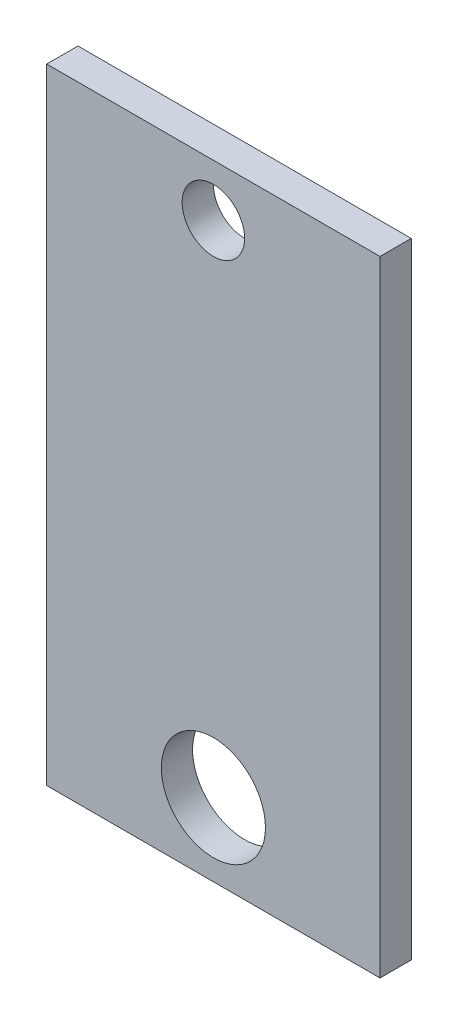
SolidWorks part; units mm, degrees
ref_plane "Спереди (XY) " through (0, 0, 0) normal (0, 0, 1) x (1, 0, 0)
ref_plane "Сверху (XZ)" through (0, 0, 0) normal (0, 1, 0) x (1, 0, 0)
ref_plane "Справа (ZY)" through (0, 0, 0) normal (1, 0, 0) x (0, 0, -1)
sketch "Эскиз1" plane through (0, 0, 0) normal (0, 0, 1) x (1, 0, 0)
  line L1 (0, 0) -> (16, 0)
  line L2 (0, 0) -> (0, 30)
  line L3 (0, 30) -> (16, 30)
  line L4 (16, 0) -> (16, 30)
  dimension "D1" = 30
  dimension "D2" = 16
extrude "Бобышка-Вытянуть1" add sketch "Эскиз1" along normal blind 1.5
sketch "Эскиз2" plane through (0, 0, 1.5) normal (0, 0, 1) x (1, 0, 0)
  line L0 (8, 30) -> (8, -49970) construction
  line L1 (16, 30) -> (0, 30) construction
  circle A0 centre (8, 27.5) radius 1.5
  circle A1 centre (8, 3.5) radius 2.5
  point P4 (8, 30)
  dimension "D1" = 3
  dimension "D2" = 5
  dimension "D3" = 2.5
  dimension "D4" = 24
extrude "Вырез-Вытянуть1" cut sketch "Эскиз2" against normal through all
equation "\"Mass_int\"= int ( ( \"SW-Масса\" + 0.005 ) * 100 ) / 100"
